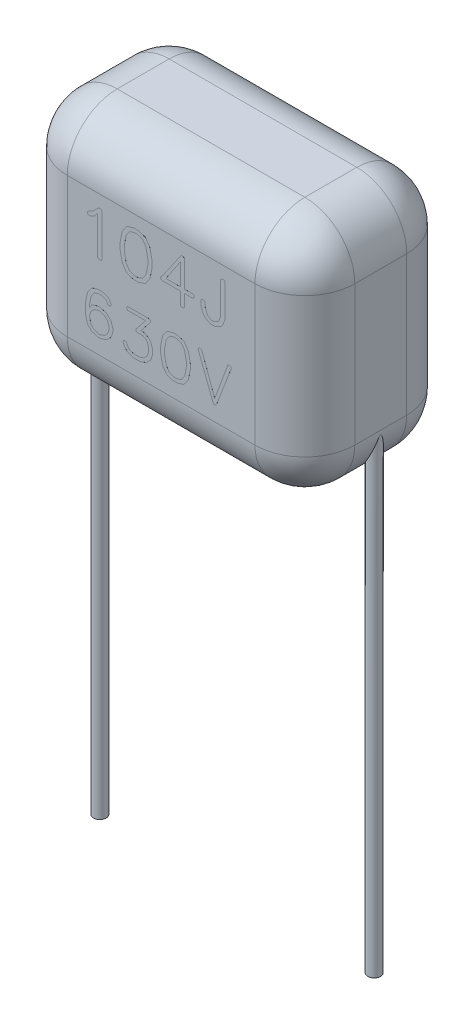
SolidWorks part; units mm, degrees
ref_plane "Front Plane" through (0, 0, 0) normal (0, 0, 1) x (1, 0, 0)
ref_plane "Top Plane" through (0, 0, 0) normal (0, 1, 0) x (1, 0, 0)
ref_plane "Right Plane" through (0, 0, 0) normal (1, 0, 0) x (0, 0, -1)
sketch "Sketch2" plane through (0, 0, 0) normal (1, 0, 0) x (0, 0, -1)
  line L0 (0, 12.4597) -> (0, -8.4662) construction
  line L2 (-1.625, 7.5) -> (1.625, 7.5)
  line L3 (-4.75, 4.375) -> (-4.75, -4.375)
  line L4 (-1.625, -7.5) -> (1.625, -7.5)
  line L5 (4.75, 4.375) -> (4.75, -4.375)
  line L6 (-4.75, 7.5) -> (4.75, -7.5) construction
  line L7 (-4.75, -7.5) -> (4.75, 7.5) construction
  arc A0 (-4.75, -4.375) -> (-1.625, -7.5) centre (-1.625, -4.375) ccw
  arc A1 (4.75, -4.375) -> (1.625, -7.5) centre (1.625, -4.375) cw
  arc A2 (4.75, 4.375) -> (1.625, 7.5) centre (1.625, 4.375) ccw
  arc A3 (-4.75, 4.375) -> (-1.625, 7.5) centre (-1.625, 4.375) cw
  point P3 (0, 0)
  dimension "D3" = 3.125
  dimension "D1" = 15
  dimension "D2" = 9.5
extrude "Boss-Extrude1" add sketch "Sketch2" along normal mid plane 18
fillet "Fillet1" radius 3.125 16 edges at (-9, -7.5, 0) (-9, -6.5847, -3.8347) (-9, 0, -4.75) (-9, 6.5847, -3.8347) (-9, 7.5, 0) (-9, 6.5847, 3.8347) (-9, 0, 4.75) (-9, -6.5847, 3.8347) (9, 0, 4.75) (9, 6.5847, 3.8347) (9, 7.5, 0) (9, 6.5847, -3.8347) (9, 0, -4.75) (9, -6.5847, -3.8347) (9, -7.5, 0) (9, -6.5847, 3.8347)
sketch "Sketch3" plane through (0, 0, 0) normal (0, 0, 1) x (1, 0, 0)
  line L0 (-5.875, 0.875) -> (5.875, 0.875) construction
  line L1 (-5.875, 4.375) -> (-5.875, -4.375) construction
  line L2 (5.875, -4.375) -> (5.875, 4.375) construction
  line L3 (-5.875, -3.375) -> (5.875, -3.375) construction
  line L4 (5.875, -4.375) -> (-5.875, -4.375) construction
  line L5 (5.875, 4.375) -> (-5.875, 4.375) construction
  text T0 "104J" font "SWSimp" height 2.8
  text T1 "630V" font "SWSimp" height 2.6
  dimension "D1" = 1
  dimension "D2" = 3.5
extrude "Boss-Extrude2" add sketch "Sketch3" along normal blind 0.001 from surface starting at face at (0, 0, 4.75)
sketch "Sketch4" plane through (0, 0, 0) normal (0, 1, 0) x (1, 0, 0)
  line L0 (0, 6.5305) -> (0, -6.6049) construction
  line L1 (-9, -1.625) -> (-9, 1.625) construction
  circle A0 centre (-8.59, 0) radius 0.4
  circle A1 centre (8.59, 0) radius 0.4
  dimension "D1" = 0.41
  dimension "D2" = 0.8
extrude "Boss-Extrude3" add sketch "Sketch4" against normal blind 34
